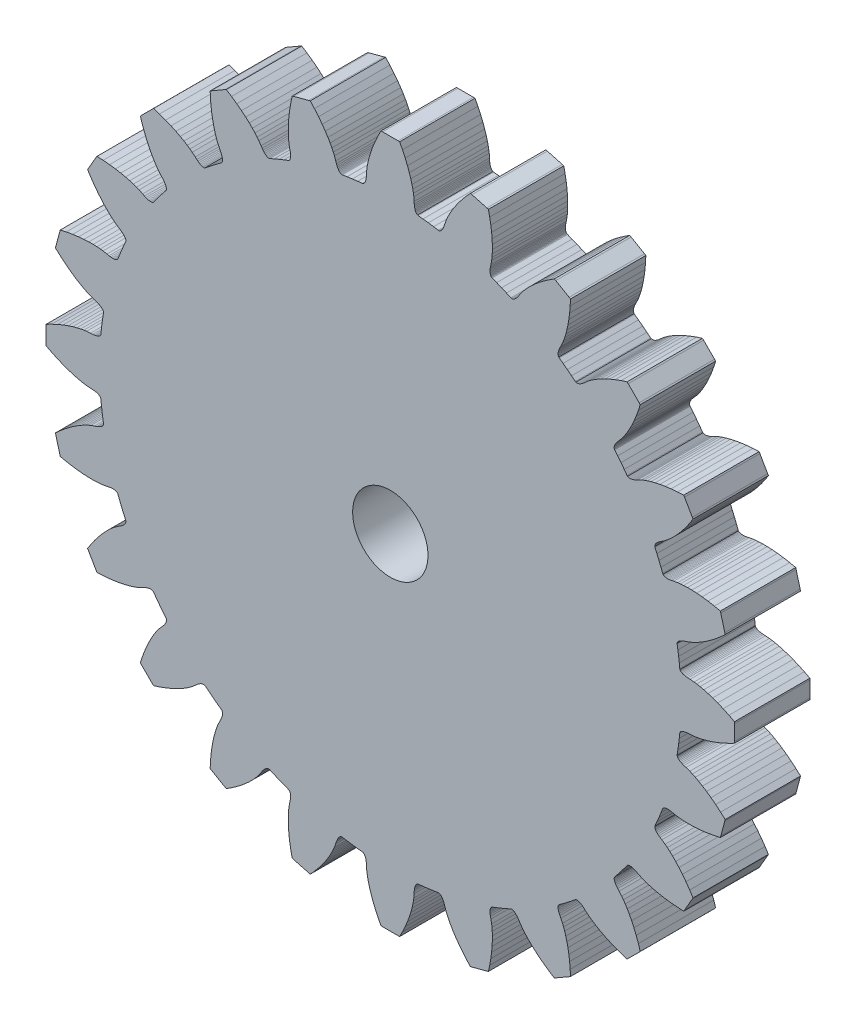
SolidWorks part; units mm, degrees
ref_plane "Front Plane" through (0, 0, 0) normal (0, 0, 1) x (1, 0, 0)
ref_plane "Top Plane" through (0, 0, 0) normal (0, 1, 0) x (1, 0, 0)
ref_plane "Right Plane" through (0, 0, 0) normal (1, 0, 0) x (0, 0, -1)
sketch "Sketch2" plane through (0, 0, 0) normal (0, 0, 1) x (1, 0, 0)
  line L1176 (3.2896, 23.0036) -> (3.0389, 22.7942)
  line L1177 (3.0389, 22.7942) -> (2.8021, 22.6117)
  line L1178 (2.8021, 22.6117) -> (2.5789, 22.4544)
  line L1179 (2.5789, 22.4544) -> (2.3725, 22.3218)
  line L1180 (2.3725, 22.3218) -> (2.182, 22.2103)
  line L1181 (2.182, 22.2103) -> (2.0109, 22.1191)
  line L1182 (2.0109, 22.1191) -> (1.8618, 22.048)
  line L1183 (1.8618, 22.048) -> (1.7314, 21.9922)
  line L1184 (1.7314, 21.9922) -> (1.5416, 21.9241)
  line L1185 (1.5416, 21.9241) -> (1.4393, 21.8922)
  line L1186 (1.4393, 21.8922) -> (1.3698, 21.8662)
  line L1187 (1.3698, 21.8662) -> (1.3083, 21.8387)
  line L1188 (1.3083, 21.8387) -> (1.2546, 21.8097)
  line L1189 (1.2546, 21.8097) -> (1.2083, 21.7799)
  line L1190 (1.2083, 21.7799) -> (1.1698, 21.7495)
  line L1191 (1.1698, 21.7495) -> (1.1387, 21.7184)
  line L1192 (1.1387, 21.7184) -> (1.1155, 21.6879)
  line L1193 (1.1155, 21.6879) -> (1.1004, 21.6575)
  line L1194 (1.1004, 21.6575) -> (1.0924, 21.627)
  line L1195 (1.0924, 21.627) -> (1.093, 21.5916)
  line L1196 (1.093, 21.5916) -> (1.1307, 21.3526)
  line L1197 (1.1307, 21.3526) -> (1.1683, 21.0852)
  line L1198 (1.1683, 21.0852) -> (1.2011, 20.818)
  line L1199 (1.2011, 20.818) -> (1.2264, 20.5774)
  line L1200 (1.2264, 20.5774) -> (1.2351, 20.542)
  line L1201 (1.2351, 20.542) -> (1.2503, 20.5151)
  line L1202 (1.2503, 20.5151) -> (1.2736, 20.4896)
  line L1203 (1.2736, 20.4896) -> (1.304, 20.4665)
  line L1204 (1.304, 20.4665) -> (1.3417, 20.4448)
  line L1205 (1.3417, 20.4448) -> (1.3865, 20.4253)
  line L1206 (1.3865, 20.4253) -> (1.4393, 20.4086)
  line L1207 (1.4393, 20.4086) -> (1.4988, 20.3942)
  line L1208 (1.4988, 20.3942) -> (1.5655, 20.384)
  line L1209 (1.5655, 20.384) -> (1.6388, 20.3767)
  line L1210 (1.6388, 20.3767) -> (1.7459, 20.3724)
  line L1211 (1.7459, 20.3724) -> (1.9474, 20.3558)
  line L1212 (1.9474, 20.3558) -> (2.0872, 20.3354)
  line L1213 (2.0872, 20.3354) -> (2.2499, 20.305)
  line L1214 (2.2499, 20.305) -> (2.4391, 20.2616)
  line L1215 (2.4391, 20.2616) -> (2.6514, 20.203)
  line L1216 (2.6514, 20.203) -> (2.8854, 20.1275)
  line L1217 (2.8854, 20.1275) -> (3.1418, 20.034)
  line L1218 (3.1418, 20.034) -> (3.4178, 19.9188)
  line L1219 (3.4178, 19.9188) -> (3.7134, 19.7813)
  line L1220 (3.7134, 19.7813) -> (3.9915, 19.6379)
  line L1221 (3.9915, 19.6379) -> (3.9938, 19.5596)
  line L1222 (3.9938, 19.5596) -> (3.9938, 18.7742)
  line L1223 (3.9938, 18.7742) -> (3.9915, 18.6954)
  line L1224 (3.9915, 18.6954) -> (3.7134, 18.5525)
  line L1225 (3.7134, 18.5525) -> (3.4178, 18.415)
  line L1226 (3.4178, 18.415) -> (3.1418, 18.2998)
  line L1227 (3.1418, 18.2998) -> (2.8854, 18.2056)
  line L1228 (2.8854, 18.2056) -> (2.6514, 18.131)
  line L1229 (2.6514, 18.131) -> (2.4391, 18.0722)
  line L1230 (2.4391, 18.0722) -> (2.2499, 18.0288)
  line L1231 (2.2499, 18.0288) -> (2.0872, 17.9984)
  line L1232 (2.0872, 17.9984) -> (1.9474, 17.9781)
  line L1233 (1.9474, 17.9781) -> (1.7459, 17.9616)
  line L1234 (1.7459, 17.9616) -> (1.6388, 17.9571)
  line L1235 (1.6388, 17.9571) -> (1.5655, 17.9498)
  line L1236 (1.5655, 17.9498) -> (1.4988, 17.9391)
  line L1237 (1.4988, 17.9391) -> (1.4393, 17.9252)
  line L1238 (1.4393, 17.9252) -> (1.3865, 17.9085)
  line L1239 (1.3865, 17.9085) -> (1.3417, 17.889)
  line L1240 (1.3417, 17.889) -> (1.304, 17.8673)
  line L1241 (1.304, 17.8673) -> (1.2736, 17.8434)
  line L1242 (1.2736, 17.8434) -> (1.2503, 17.818)
  line L1243 (1.2503, 17.818) -> (1.2351, 17.7913)
  line L1244 (1.2351, 17.7913) -> (1.2264, 17.7565)
  line L1245 (1.2264, 17.7565) -> (1.2011, 17.516)
  line L1246 (1.2011, 17.516) -> (1.1683, 17.2478)
  line L1247 (1.1683, 17.2478) -> (1.1307, 16.9813)
  line L1248 (1.1307, 16.9813) -> (1.093, 16.7423)
  line L1249 (1.093, 16.7423) -> (1.0924, 16.706)
  line L1250 (1.0924, 16.706) -> (1.1004, 16.6763)
  line L1251 (1.1004, 16.6763) -> (1.1155, 16.6459)
  line L1252 (1.1155, 16.6459) -> (1.1387, 16.6155)
  line L1253 (1.1387, 16.6155) -> (1.1698, 16.5843)
  line L1254 (1.1698, 16.5843) -> (1.2083, 16.5539)
  line L1255 (1.2083, 16.5539) -> (1.2546, 16.5243)
  line L1256 (1.2546, 16.5243) -> (1.3083, 16.4953)
  line L1257 (1.3083, 16.4953) -> (1.3698, 16.4676)
  line L2458 (1.3698, 16.4676) -> (1.4393, 16.4416)
  line L2459 (1.4393, 16.4416) -> (1.5416, 16.4097)
  line L2460 (1.5416, 16.4097) -> (1.7314, 16.3416)
  line L2461 (1.7314, 16.3416) -> (1.8618, 16.2859)
  line L2462 (1.8618, 16.2859) -> (2.0109, 16.2142)
  line L2463 (2.0109, 16.2142) -> (2.182, 16.1235)
  line L2464 (2.182, 16.1235) -> (2.3725, 16.012)
  line L2465 (2.3725, 16.012) -> (2.5789, 15.8788)
  line L2466 (2.5789, 15.8788) -> (2.8021, 15.7215)
  line L2467 (2.8021, 15.7215) -> (3.0389, 15.5396)
  line L2468 (3.0389, 15.5396) -> (3.2896, 15.3296)
  line L2469 (3.2896, 15.3296) -> (3.5207, 15.1195)
  line L2470 (3.5207, 15.1195) -> (3.5018, 15.0434)
  line L2471 (3.5018, 15.0434) -> (3.2991, 14.2842)
  line L2472 (3.2991, 14.2842) -> (3.2766, 14.2089)
  line L2473 (3.2766, 14.2089) -> (2.9715, 14.1429)
  line L2474 (2.9715, 14.1429) -> (2.65, 14.0864)
  line L2475 (2.65, 14.0864) -> (2.3537, 14.0466)
  line L2476 (2.3537, 14.0466) -> (2.0811, 14.0219)
  line L2477 (2.0811, 14.0219) -> (1.8364, 14.0105)
  line L2478 (1.8364, 14.0105) -> (1.6155, 14.009)
  line L2479 (1.6155, 14.009) -> (1.4221, 14.0155)
  line L2480 (1.4221, 14.0155) -> (1.2569, 14.0285)
  line L2481 (1.2569, 14.0285) -> (1.1163, 14.0452)
  line L2482 (1.1163, 14.0452) -> (0.9179, 14.0814)
  line L2483 (0.9179, 14.0814) -> (0.8126, 14.1046)
  line L2484 (0.8126, 14.1046) -> (0.7404, 14.1169)
  line L2485 (0.7404, 14.1169) -> (0.6731, 14.1234)
  line L2486 (0.6731, 14.1234) -> (0.6121, 14.1256)
  line L2487 (0.6121, 14.1256) -> (0.5572, 14.1226)
  line L2488 (0.5572, 14.1226) -> (0.5086, 14.1162)
  line L2489 (0.5086, 14.1162) -> (0.4664, 14.1046)
  line L2490 (0.4664, 14.1046) -> (0.431, 14.0894)
  line L2491 (0.431, 14.0894) -> (0.402, 14.0712)
  line L2492 (0.402, 14.0712) -> (0.3801, 14.0488)
  line L2493 (0.3801, 14.0488) -> (0.3629, 14.0177)
  line L2494 (0.3629, 14.0177) -> (0.276, 13.7916)
  line L2495 (0.276, 13.7916) -> (0.1753, 13.5416)
  line L2496 (0.1753, 13.5416) -> (0.0703, 13.2939)
  line L2497 (0.0703, 13.2939) -> (-0.0283, 13.0723)
  line L2498 (-0.0283, 13.0723) -> (-0.0383, 13.0382)
  line L2499 (-0.0383, 13.0382) -> (-0.0383, 13.007)
  line L2500 (-0.0383, 13.007) -> (-0.0311, 12.9737)
  line L2501 (-0.0311, 12.9737) -> (-0.0167, 12.9376)
  line L2502 (-0.0167, 12.9376) -> (0.0051, 12.8999)
  line L2503 (0.0051, 12.8999) -> (0.0339, 12.8608)
  line L2504 (0.0339, 12.8608) -> (0.0709, 12.8202)
  line L2505 (0.0709, 12.8202) -> (0.1159, 12.7781)
  line L2506 (0.1159, 12.7781) -> (0.1681, 12.7354)
  line L2507 (0.1681, 12.7354) -> (0.2282, 12.6927)
  line L2508 (0.2282, 12.6927) -> (0.3186, 12.6354)
  line L2509 (0.3186, 12.6354) -> (0.4846, 12.5202)
  line L2510 (0.4846, 12.5202) -> (0.5955, 12.4326)
  line L2511 (0.5955, 12.4326) -> (0.7214, 12.3254)
  line L2512 (0.7214, 12.3254) -> (0.8635, 12.1928)
  line L2513 (0.8635, 12.1928) -> (1.0185, 12.0356)
  line L2514 (1.0185, 12.0356) -> (1.1836, 11.8538)
  line L2515 (1.1836, 11.8538) -> (1.3582, 11.6444)
  line L2516 (1.3582, 11.6444) -> (1.5401, 11.4068)
  line L2517 (1.5401, 11.4068) -> (1.727, 11.1395)
  line L2518 (1.727, 11.1395) -> (1.8965, 10.8765)
  line L2519 (1.8965, 10.8765) -> (1.8588, 10.8077)
  line L2520 (1.8588, 10.8077) -> (1.4663, 10.1281)
  line L2521 (1.4663, 10.1281) -> (1.4257, 10.0608)
  line L2522 (1.4257, 10.0608) -> (1.1128, 10.0753)
  line L2523 (1.1128, 10.0753) -> (0.7882, 10.1042)
  line L2524 (0.7882, 10.1042) -> (0.4911, 10.1426)
  line L2525 (0.4911, 10.1426) -> (0.2224, 10.1897)
  line L2526 (0.2224, 10.1897) -> (-0.0174, 10.2412)
  line L2527 (-0.0174, 10.2412) -> (-0.231, 10.2969)
  line L2528 (-0.231, 10.2969) -> (-0.4165, 10.3542)
  line L2529 (-0.4165, 10.3542) -> (-0.573, 10.4092)
  line L2530 (-0.573, 10.4092) -> (-0.7041, 10.4614)
  line L2531 (-0.7041, 10.4614) -> (-0.8868, 10.5476)
  line L2532 (-0.8868, 10.5476) -> (-0.9816, 10.5976)
  line L2533 (-0.9816, 10.5976) -> (-1.0492, 10.628)
  line L2534 (-1.0492, 10.628) -> (-1.1119, 10.6519)
  line L2535 (-1.1119, 10.6519) -> (-1.1708, 10.6693)
  line L2536 (-1.1708, 10.6693) -> (-1.2243, 10.6809)
  line L2537 (-1.2243, 10.6809) -> (-1.2729, 10.6867)
  line L2538 (-1.2729, 10.6867) -> (-1.3163, 10.6867)
  line L2539 (-1.3163, 10.6867) -> (-1.3548, 10.6816)
  line L2540 (-1.3548, 10.6816) -> (-1.3874, 10.6715)
  line L2541 (-1.3874, 10.6715) -> (-1.4141, 10.6555)
  line L2542 (-1.4141, 10.6555) -> (-1.4388, 10.6295)
  line L2543 (-1.4388, 10.6295) -> (-1.5809, 10.4339)
  line L2544 (-1.5809, 10.4339) -> (-1.7431, 10.2187)
  line L2545 (-1.7431, 10.2187) -> (-1.9089, 10.0064)
  line L2546 (-1.9089, 10.0064) -> (-2.0618, 9.8181)
  line L2547 (-2.0618, 9.8181) -> (-2.0799, 9.7877)
  line L2548 (-2.0799, 9.7877) -> (-2.0885, 9.7572)
  line L2549 (-2.0885, 9.7572) -> (-2.09, 9.7232)
  line L2550 (-2.09, 9.7232) -> (-2.0856, 9.6848)
  line L2551 (-2.0856, 9.6848) -> (-2.0741, 9.6428)
  line L2552 (-2.0741, 9.6428) -> (-2.056, 9.5971)
  line L2553 (-2.056, 9.5971) -> (-2.0307, 9.5486)
  line L2554 (-2.0307, 9.5486) -> (-1.9988, 9.4964)
  line L2555 (-1.9988, 9.4964) -> (-1.959, 9.4421)
  line L2556 (-1.959, 9.4421) -> (-1.9119, 9.3849)
  line L2557 (-1.9119, 9.3849) -> (-1.8394, 9.3059)
  line L2558 (-1.8394, 9.3059) -> (-1.7089, 9.1516)
  line L2559 (-1.7089, 9.1516) -> (-1.6243, 9.0386)
  line L2560 (-1.6243, 9.0386) -> (-1.5308, 8.9017)
  line L2561 (-1.5308, 8.9017) -> (-1.428, 8.7372)
  line L2562 (-1.428, 8.7372) -> (-1.3186, 8.546)
  line L2563 (-1.3186, 8.546) -> (-1.2062, 8.3272)
  line L2564 (-1.2062, 8.3272) -> (-1.0917, 8.0794)
  line L2565 (-1.0917, 8.0794) -> (-0.9773, 7.8034)
  line L2566 (-0.9773, 7.8034) -> (-0.8657, 7.497)
  line L2567 (-0.8657, 7.497) -> (-0.7709, 7.1985)
  line L2568 (-0.7709, 7.1985) -> (-0.8252, 7.142)
  line L2569 (-0.8252, 7.142) -> (-1.3802, 6.5871)
  line L2570 (-1.3802, 6.5871) -> (-1.4365, 6.5328)
  line L2571 (-1.4365, 6.5328) -> (-1.7351, 6.6277)
  line L2572 (-1.7351, 6.6277) -> (-2.0415, 6.7392)
  line L2573 (-2.0415, 6.7392) -> (-2.3174, 6.8537)
  line L2574 (-2.3174, 6.8537) -> (-2.5652, 6.9682)
  line L2575 (-2.5652, 6.9682) -> (-2.7841, 7.0805)
  line L2576 (-2.7841, 7.0805) -> (-2.9753, 7.1898)
  line L2577 (-2.9753, 7.1898) -> (-3.1398, 7.2927)
  line L2578 (-3.1398, 7.2927) -> (-3.2767, 7.3862)
  line L2579 (-3.2767, 7.3862) -> (-3.3898, 7.4709)
  line L2580 (-3.3898, 7.4709) -> (-3.544, 7.6013)
  line L2581 (-3.544, 7.6013) -> (-3.623, 7.6738)
  line L2582 (-3.623, 7.6738) -> (-3.6802, 7.7209)
  line L2583 (-3.6802, 7.7209) -> (-3.7345, 7.7607)
  line L2584 (-3.7345, 7.7607) -> (-3.7866, 7.7926)
  line L2585 (-3.7866, 7.7926) -> (-3.8352, 7.8179)
  line L2586 (-3.8352, 7.8179) -> (-3.8809, 7.836)
  line L2587 (-3.8809, 7.836) -> (-3.9229, 7.8476)
  line L2588 (-3.9229, 7.8476) -> (-3.9613, 7.852)
  line L2589 (-3.9613, 7.852) -> (-3.9953, 7.8505)
  line L2590 (-3.9953, 7.8505) -> (-4.0256, 7.8418)
  line L2591 (-4.0256, 7.8418) -> (-4.0561, 7.8237)
  line L2592 (-4.0561, 7.8237) -> (-4.2445, 7.6709)
  line L2593 (-4.2445, 7.6709) -> (-4.4569, 7.505)
  line L2594 (-4.4569, 7.505) -> (-4.672, 7.3427)
  line L2595 (-4.672, 7.3427) -> (-4.8674, 7.2007)
  line L2596 (-4.8674, 7.2007) -> (-4.8936, 7.1761)
  line L2597 (-4.8936, 7.1761) -> (-4.9096, 7.1493)
  line L2598 (-4.9096, 7.1493) -> (-4.9197, 7.1167)
  line L2599 (-4.9197, 7.1167) -> (-4.9248, 7.0783)
  line L2600 (-4.9248, 7.0783) -> (-4.9248, 7.0348)
  line L2601 (-4.9248, 7.0348) -> (-4.9191, 6.9863)
  line L2602 (-4.9191, 6.9863) -> (-4.9073, 6.9327)
  line L2603 (-4.9073, 6.9327) -> (-4.8901, 6.874)
  line L2604 (-4.8901, 6.874) -> (-4.8662, 6.8109)
  line L2605 (-4.8662, 6.8109) -> (-4.8357, 6.7436)
  line L2606 (-4.8357, 6.7436) -> (-4.7857, 6.6487)
  line L2607 (-4.7857, 6.6487) -> (-4.6994, 6.4661)
  line L2608 (-4.6994, 6.4661) -> (-4.6473, 6.335)
  line L2609 (-4.6473, 6.335) -> (-4.5922, 6.1785)
  line L2610 (-4.5922, 6.1785) -> (-4.5349, 5.9931)
  line L2611 (-4.5349, 5.9931) -> (-4.4794, 5.7793)
  line L2612 (-4.4794, 5.7793) -> (-4.4277, 5.5396)
  line L2613 (-4.4277, 5.5396) -> (-4.3807, 5.2708)
  line L2614 (-4.3807, 5.2708) -> (-4.3422, 4.9738)
  line L2615 (-4.3422, 4.9738) -> (-4.3134, 4.6492)
  line L2616 (-4.3134, 4.6492) -> (-4.2988, 4.3363)
  line L2617 (-4.2988, 4.3363) -> (-4.3661, 4.2957)
  line L2618 (-4.3661, 4.2957) -> (-5.0456, 3.9031)
  line L2619 (-5.0456, 3.9031) -> (-5.1144, 3.8654)
  line L2620 (-5.1144, 3.8654) -> (-5.3775, 4.0349)
  line L2621 (-5.3775, 4.0349) -> (-5.6449, 4.2218)
  line L2622 (-5.6449, 4.2218) -> (-5.8825, 4.4037)
  line L2623 (-5.8825, 4.4037) -> (-6.0918, 4.5782)
  line L2624 (-6.0918, 4.5782) -> (-6.2736, 4.7434)
  line L2625 (-6.2736, 4.7434) -> (-6.4309, 4.8984)
  line L2626 (-6.4309, 4.8984) -> (-6.5635, 5.0404)
  line L2627 (-6.5635, 5.0404) -> (-6.6707, 5.1665)
  line L2628 (-6.6707, 5.1665) -> (-6.7584, 5.2773)
  line L2629 (-6.7584, 5.2773) -> (-6.8735, 5.4432)
  line L2630 (-6.8735, 5.4432) -> (-6.9307, 5.5338)
  line L2631 (-6.9307, 5.5338) -> (-6.9735, 5.5939)
  line L2632 (-6.9735, 5.5939) -> (-7.0161, 5.6461)
  line L2633 (-7.0161, 5.6461) -> (-7.0582, 5.691)
  line L2634 (-7.0582, 5.691) -> (-7.0989, 5.7279)
  line L2635 (-7.0989, 5.7279) -> (-7.138, 5.7569)
  line L2636 (-7.138, 5.7569) -> (-7.1757, 5.7786)
  line L2637 (-7.1757, 5.7786) -> (-7.2117, 5.7931)
  line L2638 (-7.2117, 5.7931) -> (-7.2451, 5.8004)
  line L2639 (-7.2451, 5.8004) -> (-7.2764, 5.8004)
  line L2640 (-7.2764, 5.8004) -> (-7.3103, 5.7902)
  line L2641 (-7.3103, 5.7902) -> (-7.5321, 5.6917)
  line L2642 (-7.5321, 5.6917) -> (-7.7799, 5.5867)
  line L2643 (-7.7799, 5.5867) -> (-8.0296, 5.486)
  line L2644 (-8.0296, 5.486) -> (-8.2557, 5.399)
  line L2645 (-8.2557, 5.399) -> (-8.2869, 5.3816)
  line L2646 (-8.2869, 5.3816) -> (-8.3093, 5.3599)
  line L2647 (-8.3093, 5.3599) -> (-8.3275, 5.3309)
  line L2648 (-8.3275, 5.3309) -> (-8.3427, 5.2954)
  line L2649 (-8.3427, 5.2954) -> (-8.3542, 5.2534)
  line L2650 (-8.3542, 5.2534) -> (-8.3607, 5.2049)
  line L2651 (-8.3607, 5.2049) -> (-8.3637, 5.1498)
  line L2652 (-8.3637, 5.1498) -> (-8.3614, 5.089)
  line L2653 (-8.3614, 5.089) -> (-8.355, 5.0216)
  line L2654 (-8.355, 5.0216) -> (-8.3427, 4.9492)
  line L2655 (-8.3427, 4.9492) -> (-8.3195, 4.8441)
  line L2656 (-8.3195, 4.8441) -> (-8.2832, 4.6456)
  line L2657 (-8.2832, 4.6456) -> (-8.2666, 4.5051)
  line L2658 (-8.2666, 4.5051) -> (-8.2535, 4.3399)
  line L2659 (-8.2535, 4.3399) -> (-8.247, 4.1465)
  line L2660 (-8.247, 4.1465) -> (-8.2485, 3.9255)
  line L2661 (-8.2485, 3.9255) -> (-8.2599, 3.6807)
  line L2662 (-8.2599, 3.6807) -> (-8.2846, 3.4083)
  line L2663 (-8.2846, 3.4083) -> (-8.3246, 3.112)
  line L2664 (-8.3246, 3.112) -> (-8.381, 2.7903)
  line L2665 (-8.381, 2.7903) -> (-8.4469, 2.4853)
  line L2666 (-8.4469, 2.4853) -> (-8.5222, 2.4629)
  line L2667 (-8.5222, 2.4629) -> (-9.2814, 2.2601)
  line L2668 (-9.2814, 2.2601) -> (-9.3575, 2.2412)
  line L2669 (-9.3575, 2.2412) -> (-9.5676, 2.4723)
  line L2670 (-9.5676, 2.4723) -> (-9.7777, 2.723)
  line L2671 (-9.7777, 2.723) -> (-9.9595, 2.9598)
  line L2672 (-9.9595, 2.9598) -> (-10.1168, 3.183)
  line L2673 (-10.1168, 3.183) -> (-10.2502, 3.3894)
  line L2674 (-10.2502, 3.3894) -> (-10.3615, 3.58)
  line L2675 (-10.3615, 3.58) -> (-10.4523, 3.7509)
  line L2676 (-10.4523, 3.7509) -> (-10.5239, 3.9002)
  line L2677 (-10.5239, 3.9002) -> (-10.5797, 4.0306)
  line L2678 (-10.5797, 4.0306) -> (-10.6477, 4.2204)
  line L2679 (-10.6477, 4.2204) -> (-10.6796, 4.3225)
  line L2680 (-10.6796, 4.3225) -> (-10.7058, 4.3921)
  line L2681 (-10.7058, 4.3921) -> (-10.7333, 4.4536)
  line L2682 (-10.7333, 4.4536) -> (-10.7624, 4.5072)
  line L2683 (-10.7624, 4.5072) -> (-10.792, 4.5536)
  line L2684 (-10.792, 4.5536) -> (-10.8225, 4.592)
  line L2685 (-10.8225, 4.592) -> (-10.8536, 4.6232)
  line L2686 (-10.8536, 4.6232) -> (-10.884, 4.6463)
  line L2687 (-10.884, 4.6463) -> (-10.9145, 4.6616)
  line L2688 (-10.9145, 4.6616) -> (-10.9441, 4.6695)
  line L2689 (-10.9441, 4.6695) -> (-10.9803, 4.6688)
  line L2690 (-10.9803, 4.6688) -> (-11.2193, 4.6311)
  line L2691 (-11.2193, 4.6311) -> (-11.486, 4.5935)
  line L2692 (-11.486, 4.5935) -> (-11.754, 4.5608)
  line L2693 (-11.754, 4.5608) -> (-11.9946, 4.5355)
  line L2694 (-11.9946, 4.5355) -> (-12.0294, 4.5268)
  line L2695 (-12.0294, 4.5268) -> (-12.0561, 4.5116)
  line L2696 (-12.0561, 4.5116) -> (-12.0815, 4.4884)
  line L2697 (-12.0815, 4.4884) -> (-12.1054, 4.458)
  line L2698 (-12.1054, 4.458) -> (-12.1272, 4.4203)
  line L2699 (-12.1272, 4.4203) -> (-12.1465, 4.3754)
  line L2700 (-12.1465, 4.3754) -> (-12.1632, 4.3225)
  line L2701 (-12.1632, 4.3225) -> (-12.1772, 4.2631)
  line L2702 (-12.1772, 4.2631) -> (-12.1879, 4.1965)
  line L2703 (-12.1879, 4.1965) -> (-12.1951, 4.1233)
  line L2704 (-12.1951, 4.1233) -> (-12.1997, 4.0161)
  line L2705 (-12.1997, 4.0161) -> (-12.2161, 3.8147)
  line L2706 (-12.2161, 3.8147) -> (-12.2365, 3.6749)
  line L2707 (-12.2365, 3.6749) -> (-12.267, 3.5119)
  line L2708 (-12.267, 3.5119) -> (-12.3104, 3.3228)
  line L2709 (-12.3104, 3.3228) -> (-12.3691, 3.1105)
  line L2710 (-12.3691, 3.1105) -> (-12.4436, 2.8765)
  line L2711 (-12.4436, 2.8765) -> (-12.5379, 2.6201)
  line L2712 (-12.5379, 2.6201) -> (-12.653, 2.3441)
  line L2713 (-12.653, 2.3441) -> (-12.7907, 2.0485)
  line L2714 (-12.7907, 2.0485) -> (-12.9334, 1.7703)
  line L2715 (-12.9334, 1.7703) -> (-13.0123, 1.7681)
  line L2716 (-13.0123, 1.7681) -> (-13.7977, 1.7681)
  line L2717 (-13.7977, 1.7681) -> (-13.876, 1.7703)
  line L2718 (-13.876, 1.7703) -> (-14.0193, 2.0485)
  line L2719 (-14.0193, 2.0485) -> (-14.1569, 2.3441)
  line L2720 (-14.1569, 2.3441) -> (-14.272, 2.6201)
  line L2721 (-14.272, 2.6201) -> (-14.3655, 2.8765)
  line L2722 (-14.3655, 2.8765) -> (-14.4411, 3.1105)
  line L2723 (-14.4411, 3.1105) -> (-14.4997, 3.3228)
  line L2724 (-14.4997, 3.3228) -> (-14.5431, 3.5119)
  line L2725 (-14.5431, 3.5119) -> (-14.5735, 3.6749)
  line L2726 (-14.5735, 3.6749) -> (-14.5938, 3.8147)
  line L2727 (-14.5938, 3.8147) -> (-14.6105, 4.0161)
  line L2728 (-14.6105, 4.0161) -> (-14.6148, 4.1233)
  line L2729 (-14.6148, 4.1233) -> (-14.622, 4.1965)
  line L2730 (-14.622, 4.1965) -> (-14.6322, 4.2631)
  line L2731 (-14.6322, 4.2631) -> (-14.6467, 4.3225)
  line L2732 (-14.6467, 4.3225) -> (-14.6634, 4.3754)
  line L2733 (-14.6634, 4.3754) -> (-14.6829, 4.4203)
  line L2734 (-14.6829, 4.4203) -> (-14.7047, 4.458)
  line L2735 (-14.7047, 4.458) -> (-14.7278, 4.4884)
  line L2736 (-14.7278, 4.4884) -> (-14.7533, 4.5116)
  line L2737 (-14.7533, 4.5116) -> (-14.78, 4.5268)
  line L2738 (-14.78, 4.5268) -> (-14.8155, 4.5355)
  line L2739 (-14.8155, 4.5355) -> (-15.056, 4.5608)
  line L2740 (-15.056, 4.5608) -> (-15.3233, 4.5935)
  line L2741 (-15.3233, 4.5935) -> (-15.5906, 4.6311)
  line L2742 (-15.5906, 4.6311) -> (-15.8296, 4.6688)
  line L2743 (-15.8296, 4.6688) -> (-15.8652, 4.6695)
  line L2744 (-15.8652, 4.6695) -> (-15.8956, 4.6616)
  line L2745 (-15.8956, 4.6616) -> (-15.926, 4.6463)
  line L2746 (-15.926, 4.6463) -> (-15.9565, 4.6232)
  line L2747 (-15.9565, 4.6232) -> (-15.9876, 4.592)
  line L2748 (-15.9876, 4.592) -> (-16.018, 4.5536)
  line L2749 (-16.018, 4.5536) -> (-16.0478, 4.5072)
  line L2750 (-16.0478, 4.5072) -> (-16.0768, 4.4536)
  line L2751 (-16.0768, 4.4536) -> (-16.1043, 4.3921)
  line L2752 (-16.1043, 4.3921) -> (-16.1303, 4.3225)
  line L2753 (-16.1303, 4.3225) -> (-16.1623, 4.2204)
  line L2754 (-16.1623, 4.2204) -> (-16.2304, 4.0306)
  line L2755 (-16.2304, 4.0306) -> (-16.286, 3.9002)
  line L2756 (-16.286, 3.9002) -> (-16.3571, 3.7509)
  line L2757 (-16.3571, 3.7509) -> (-16.4484, 3.58)
  line L2758 (-16.4484, 3.58) -> (-16.5599, 3.3894)
  line L2759 (-16.5599, 3.3894) -> (-16.6925, 3.183)
  line L2760 (-16.6925, 3.183) -> (-16.8497, 2.9598)
  line L2761 (-16.8497, 2.9598) -> (-17.0323, 2.723)
  line L2762 (-17.0323, 2.723) -> (-17.2416, 2.4723)
  line L2763 (-17.2416, 2.4723) -> (-17.4524, 2.2412)
  line L2764 (-17.4524, 2.2412) -> (-17.5292, 2.2601)
  line L2765 (-17.5292, 2.2601) -> (-18.2878, 2.4629)
  line L2766 (-18.2878, 2.4629) -> (-18.3624, 2.4853)
  line L2767 (-18.3624, 2.4853) -> (-18.429, 2.7903)
  line L2768 (-18.429, 2.7903) -> (-18.4855, 3.112)
  line L2769 (-18.4855, 3.112) -> (-18.5246, 3.4083)
  line L2770 (-18.5246, 3.4083) -> (-18.5492, 3.6807)
  line L2771 (-18.5492, 3.6807) -> (-18.5615, 3.9255)
  line L2772 (-18.5615, 3.9255) -> (-18.563, 4.1465)
  line L2773 (-18.563, 4.1465) -> (-18.5557, 4.3399)
  line L2774 (-18.5557, 4.3399) -> (-18.5435, 4.5051)
  line L2775 (-18.5435, 4.5051) -> (-18.5261, 4.6456)
  line L2776 (-18.5261, 4.6456) -> (-18.4906, 4.8441)
  line L2777 (-18.4906, 4.8441) -> (-18.4667, 4.9492)
  line L2778 (-18.4667, 4.9492) -> (-18.4551, 5.0216)
  line L2779 (-18.4551, 5.0216) -> (-18.4479, 5.089)
  line L2780 (-18.4479, 5.089) -> (-18.4464, 5.1498)
  line L2781 (-18.4464, 5.1498) -> (-18.4485, 5.2049)
  line L2782 (-18.4485, 5.2049) -> (-18.4557, 5.2534)
  line L2783 (-18.4557, 5.2534) -> (-18.4674, 5.2954)
  line L2784 (-18.4674, 5.2954) -> (-18.4819, 5.3309)
  line L2785 (-18.4819, 5.3309) -> (-18.5007, 5.3599)
  line L2786 (-18.5007, 5.3599) -> (-18.5225, 5.3816)
  line L2787 (-18.5225, 5.3816) -> (-18.5543, 5.399)
  line L2788 (-18.5543, 5.399) -> (-18.7803, 5.486)
  line L2789 (-18.7803, 5.486) -> (-19.0303, 5.5867)
  line L2790 (-19.0303, 5.5867) -> (-19.278, 5.6917)
  line L2791 (-19.278, 5.6917) -> (-19.499, 5.7902)
  line L2792 (-19.499, 5.7902) -> (-19.5337, 5.8004)
  line L2793 (-19.5337, 5.8004) -> (-19.565, 5.8004)
  line L2794 (-19.565, 5.8004) -> (-19.5982, 5.7931)
  line L2795 (-19.5982, 5.7931) -> (-19.6337, 5.7786)
  line L2796 (-19.6337, 5.7786) -> (-19.6714, 5.7569)
  line L2797 (-19.6714, 5.7569) -> (-19.7112, 5.7279)
  line L2798 (-19.7112, 5.7279) -> (-19.7518, 5.691)
  line L2799 (-19.7518, 5.691) -> (-19.7938, 5.6461)
  line L2800 (-19.7938, 5.6461) -> (-19.8358, 5.5939)
  line L2801 (-19.8358, 5.5939) -> (-19.8793, 5.5338)
  line L2802 (-19.8793, 5.5338) -> (-19.9365, 5.4432)
  line L2803 (-19.9365, 5.4432) -> (-20.0517, 5.2773)
  line L2804 (-20.0517, 5.2773) -> (-20.1386, 5.1665)
  line L2805 (-20.1386, 5.1665) -> (-20.2466, 5.0404)
  line L2806 (-20.2466, 5.0404) -> (-20.3792, 4.8984)
  line L2807 (-20.3792, 4.8984) -> (-20.5356, 4.7434)
  line L2808 (-20.5356, 4.7434) -> (-20.7175, 4.5782)
  line L2809 (-20.7175, 4.5782) -> (-20.9276, 4.4037)
  line L2810 (-20.9276, 4.4037) -> (-21.1645, 4.2218)
  line L2811 (-21.1645, 4.2218) -> (-21.4318, 4.0349)
  line L2812 (-21.4318, 4.0349) -> (-21.6955, 3.8654)
  line L2813 (-21.6955, 3.8654) -> (-21.765, 3.9031)
  line L2814 (-21.765, 3.9031) -> (-22.4445, 4.2957)
  line L2815 (-22.4445, 4.2957) -> (-22.5112, 4.3363)
  line L2816 (-22.5112, 4.3363) -> (-22.496, 4.6492)
  line L2817 (-22.496, 4.6492) -> (-22.4677, 4.9738)
  line L2818 (-22.4677, 4.9738) -> (-22.4286, 5.2708)
  line L2819 (-22.4286, 5.2708) -> (-22.3822, 5.5396)
  line L2820 (-22.3822, 5.5396) -> (-22.3301, 5.7793)
  line L2821 (-22.3301, 5.7793) -> (-22.2743, 5.9931)
  line L2822 (-22.2743, 5.9931) -> (-22.2178, 6.1785)
  line L2823 (-22.2178, 6.1785) -> (-22.1627, 6.335)
  line L2824 (-22.1627, 6.335) -> (-22.1106, 6.4661)
  line L2825 (-22.1106, 6.4661) -> (-22.0244, 6.6487)
  line L2826 (-22.0244, 6.6487) -> (-21.9744, 6.7436)
  line L2827 (-21.9744, 6.7436) -> (-21.9439, 6.8109)
  line L2828 (-21.9439, 6.8109) -> (-21.92, 6.874)
  line L2829 (-21.92, 6.874) -> (-21.9019, 6.9327)
  line L2830 (-21.9019, 6.9327) -> (-21.8903, 6.9863)
  line L2831 (-21.8903, 6.9863) -> (-21.8846, 7.0348)
  line L2832 (-21.8846, 7.0348) -> (-21.8846, 7.0783)
  line L2833 (-21.8846, 7.0783) -> (-21.8903, 7.1167)
  line L2834 (-21.8903, 7.1167) -> (-21.9005, 7.1493)
  line L2835 (-21.9005, 7.1493) -> (-21.9164, 7.1761)
  line L2836 (-21.9164, 7.1761) -> (-21.9418, 7.2007)
  line L2837 (-21.9418, 7.2007) -> (-22.1381, 7.3427)
  line L2838 (-22.1381, 7.3427) -> (-22.3532, 7.505)
  line L2839 (-22.3532, 7.505) -> (-22.5655, 7.6709)
  line L2840 (-22.5655, 7.6709) -> (-22.7539, 7.8237)
  line L2841 (-22.7539, 7.8237) -> (-22.7843, 7.8418)
  line L2842 (-22.7843, 7.8418) -> (-22.814, 7.8505)
  line L2843 (-22.814, 7.8505) -> (-22.8488, 7.852)
  line L2844 (-22.8488, 7.852) -> (-22.8864, 7.8476)
  line L2845 (-22.8864, 7.8476) -> (-22.9285, 7.836)
  line L2846 (-22.9285, 7.836) -> (-22.9741, 7.8179)
  line L2847 (-22.9741, 7.8179) -> (-23.0234, 7.7926)
  line L2848 (-23.0234, 7.7926) -> (-23.0755, 7.7607)
  line L2849 (-23.0755, 7.7607) -> (-23.1298, 7.7209)
  line L2850 (-23.1298, 7.7209) -> (-23.1871, 7.6738)
  line L2851 (-23.1871, 7.6738) -> (-23.266, 7.6013)
  line L2852 (-23.266, 7.6013) -> (-23.4196, 7.4709)
  line L2853 (-23.4196, 7.4709) -> (-23.5334, 7.3862)
  line L2854 (-23.5334, 7.3862) -> (-23.6696, 7.2927)
  line L2855 (-23.6696, 7.2927) -> (-23.834, 7.1898)
  line L2856 (-23.834, 7.1898) -> (-24.026, 7.0805)
  line L2857 (-24.026, 7.0805) -> (-24.244, 6.9682)
  line L2858 (-24.244, 6.9682) -> (-24.4918, 6.8537)
  line L2859 (-24.4918, 6.8537) -> (-24.7685, 6.7392)
  line L2860 (-24.7685, 6.7392) -> (-25.075, 6.6277)
  line L2861 (-25.075, 6.6277) -> (-25.3727, 6.5328)
  line L2862 (-25.3727, 6.5328) -> (-25.4299, 6.5871)
  line L2863 (-25.4299, 6.5871) -> (-25.9856, 7.142)
  line L2864 (-25.9856, 7.142) -> (-26.0392, 7.1985)
  line L2865 (-26.0392, 7.1985) -> (-25.9443, 7.497)
  line L2866 (-25.9443, 7.497) -> (-25.832, 7.8034)
  line L2867 (-25.832, 7.8034) -> (-25.7183, 8.0794)
  line L2868 (-25.7183, 8.0794) -> (-25.6031, 8.3272)
  line L2869 (-25.6031, 8.3272) -> (-25.4908, 8.546)
  line L2870 (-25.4908, 8.546) -> (-25.3821, 8.7372)
  line L2871 (-25.3821, 8.7372) -> (-25.2793, 8.9017)
  line L2872 (-25.2793, 8.9017) -> (-25.1858, 9.0386)
  line L2873 (-25.1858, 9.0386) -> (-25.101, 9.1516)
  line L2874 (-25.101, 9.1516) -> (-24.9706, 9.3059)
  line L2875 (-24.9706, 9.3059) -> (-24.8975, 9.3849)
  line L2876 (-24.8975, 9.3849) -> (-24.8511, 9.4421)
  line L2877 (-24.8511, 9.4421) -> (-24.8113, 9.4964)
  line L2878 (-24.8113, 9.4964) -> (-24.7794, 9.5486)
  line L2879 (-24.7794, 9.5486) -> (-24.754, 9.5971)
  line L2880 (-24.754, 9.5971) -> (-24.7359, 9.6428)
  line L2881 (-24.7359, 9.6428) -> (-24.7243, 9.6848)
  line L2882 (-24.7243, 9.6848) -> (-24.72, 9.7232)
  line L2883 (-24.72, 9.7232) -> (-24.7214, 9.7572)
  line L2884 (-24.7214, 9.7572) -> (-24.7294, 9.7877)
  line L2885 (-24.7294, 9.7877) -> (-24.7482, 9.8181)
  line L2886 (-24.7482, 9.8181) -> (-24.9004, 10.0064)
  line L2887 (-24.9004, 10.0064) -> (-25.0663, 10.2187)
  line L2888 (-25.0663, 10.2187) -> (-25.2285, 10.4339)
  line L2889 (-25.2285, 10.4339) -> (-25.3713, 10.6295)
  line L2890 (-25.3713, 10.6295) -> (-25.3959, 10.6555)
  line L2891 (-25.3959, 10.6555) -> (-25.4227, 10.6715)
  line L2892 (-25.4227, 10.6715) -> (-25.4553, 10.6816)
  line L2893 (-25.4553, 10.6816) -> (-25.493, 10.6867)
  line L2894 (-25.493, 10.6867) -> (-25.5372, 10.6867)
  line L2895 (-25.5372, 10.6867) -> (-25.5857, 10.6809)
  line L2896 (-25.5857, 10.6809) -> (-25.6393, 10.6693)
  line L2897 (-25.6393, 10.6693) -> (-25.698, 10.6519)
  line L2898 (-25.698, 10.6519) -> (-25.761, 10.628)
  line L2899 (-25.761, 10.628) -> (-25.8284, 10.5976)
  line L2900 (-25.8284, 10.5976) -> (-25.9233, 10.5476)
  line L2901 (-25.9233, 10.5476) -> (-26.1058, 10.4614)
  line L2902 (-26.1058, 10.4614) -> (-26.237, 10.4092)
  line L2903 (-26.237, 10.4092) -> (-26.3934, 10.3542)
  line L2904 (-26.3934, 10.3542) -> (-26.5789, 10.2969)
  line L2905 (-26.5789, 10.2969) -> (-26.7919, 10.2412)
  line L2906 (-26.7919, 10.2412) -> (-27.0324, 10.1897)
  line L2907 (-27.0324, 10.1897) -> (-27.3012, 10.1426)
  line L2908 (-27.3012, 10.1426) -> (-27.5975, 10.1042)
  line L2909 (-27.5975, 10.1042) -> (-27.9227, 10.0753)
  line L2910 (-27.9227, 10.0753) -> (-28.235, 10.0608)
  line L2911 (-28.235, 10.0608) -> (-28.2762, 10.1281)
  line L2912 (-28.2762, 10.1281) -> (-28.6696, 10.8077)
  line L2913 (-28.6696, 10.8077) -> (-28.7066, 10.8765)
  line L2914 (-28.7066, 10.8765) -> (-28.5371, 11.1395)
  line L2915 (-28.5371, 11.1395) -> (-28.3501, 11.4068)
  line L2916 (-28.3501, 11.4068) -> (-28.1683, 11.6444)
  line L2917 (-28.1683, 11.6444) -> (-27.993, 11.8538)
  line L2918 (-27.993, 11.8538) -> (-27.8278, 12.0356)
  line L2919 (-27.8278, 12.0356) -> (-27.6735, 12.1928)
  line L2920 (-27.6735, 12.1928) -> (-27.5315, 12.3254)
  line L2921 (-27.5315, 12.3254) -> (-27.4055, 12.4326)
  line L2922 (-27.4055, 12.4326) -> (-27.2946, 12.5202)
  line L2923 (-27.2946, 12.5202) -> (-27.1287, 12.6354)
  line L2924 (-27.1287, 12.6354) -> (-27.0382, 12.6927)
  line L2925 (-27.0382, 12.6927) -> (-26.978, 12.7354)
  line L2926 (-26.978, 12.7354) -> (-26.9259, 12.7781)
  line L2927 (-26.9259, 12.7781) -> (-26.881, 12.8202)
  line L2928 (-26.881, 12.8202) -> (-26.844, 12.8608)
  line L2929 (-26.844, 12.8608) -> (-26.8143, 12.8999)
  line L2930 (-26.8143, 12.8999) -> (-26.7926, 12.9376)
  line L2931 (-26.7926, 12.9376) -> (-26.7781, 12.9737)
  line L2932 (-26.7781, 12.9737) -> (-26.7709, 13.007)
  line L2933 (-26.7709, 13.007) -> (-26.7716, 13.0382)
  line L2934 (-26.7716, 13.0382) -> (-26.781, 13.0723)
  line L2935 (-26.781, 13.0723) -> (-26.8803, 13.2939)
  line L2936 (-26.8803, 13.2939) -> (-26.9853, 13.5416)
  line L2937 (-26.9853, 13.5416) -> (-27.086, 13.7916)
  line L2938 (-27.086, 13.7916) -> (-27.1729, 14.0177)
  line L2939 (-27.1729, 14.0177) -> (-27.1903, 14.0488)
  line L2940 (-27.1903, 14.0488) -> (-27.212, 14.0712)
  line L2941 (-27.212, 14.0712) -> (-27.2403, 14.0894)
  line L2942 (-27.2403, 14.0894) -> (-27.2758, 14.1046)
  line L2943 (-27.2758, 14.1046) -> (-27.3185, 14.1162)
  line L2944 (-27.3185, 14.1162) -> (-27.3671, 14.1226)
  line L2945 (-27.3671, 14.1226) -> (-27.4221, 14.1256)
  line L2946 (-27.4221, 14.1256) -> (-27.483, 14.1234)
  line L2947 (-27.483, 14.1234) -> (-27.5496, 14.1169)
  line L2948 (-27.5496, 14.1169) -> (-27.6228, 14.1046)
  line L2949 (-27.6228, 14.1046) -> (-27.7271, 14.0814)
  line L2950 (-27.7271, 14.0814) -> (-27.9263, 14.0452)
  line L2951 (-27.9263, 14.0452) -> (-28.0662, 14.0285)
  line L2952 (-28.0662, 14.0285) -> (-28.232, 14.0155)
  line L2953 (-28.232, 14.0155) -> (-28.4255, 14.009)
  line L2954 (-28.4255, 14.009) -> (-28.6457, 14.0105)
  line L2955 (-28.6457, 14.0105) -> (-28.8913, 14.0219)
  line L2956 (-28.8913, 14.0219) -> (-29.163, 14.0466)
  line L2957 (-29.163, 14.0466) -> (-29.46, 14.0864)
  line L2958 (-29.46, 14.0864) -> (-29.7809, 14.1429)
  line L2959 (-29.7809, 14.1429) -> (-30.0866, 14.2089)
  line L2960 (-30.0866, 14.2089) -> (-30.1091, 14.2842)
  line L2961 (-30.1091, 14.2842) -> (-30.3126, 15.0434)
  line L2962 (-30.3126, 15.0434) -> (-30.3307, 15.1195)
  line L2963 (-30.3307, 15.1195) -> (-30.0989, 15.3296)
  line L2964 (-30.0989, 15.3296) -> (-29.849, 15.5396)
  line L2965 (-29.849, 15.5396) -> (-29.6121, 15.7215)
  line L2966 (-29.6121, 15.7215) -> (-29.389, 15.8788)
  line L2967 (-29.389, 15.8788) -> (-29.1825, 16.012)
  line L2968 (-29.1825, 16.012) -> (-28.992, 16.1235)
  line L2969 (-28.992, 16.1235) -> (-28.821, 16.2142)
  line L2970 (-28.821, 16.2142) -> (-28.6711, 16.2859)
  line L2971 (-28.6711, 16.2859) -> (-28.5414, 16.3416)
  line L2972 (-28.5414, 16.3416) -> (-28.3516, 16.4097)
  line L2973 (-28.3516, 16.4097) -> (-28.2487, 16.4416)
  line L2974 (-28.2487, 16.4416) -> (-28.1799, 16.4676)
  line L2975 (-28.1799, 16.4676) -> (-28.1183, 16.4953)
  line L2976 (-28.1183, 16.4953) -> (-28.0647, 16.5243)
  line L2977 (-28.0647, 16.5243) -> (-28.0183, 16.5539)
  line L2978 (-28.0183, 16.5539) -> (-27.98, 16.5843)
  line L2979 (-27.98, 16.5843) -> (-27.9488, 16.6155)
  line L2980 (-27.9488, 16.6155) -> (-27.9256, 16.6459)
  line L2981 (-27.9256, 16.6459) -> (-27.9097, 16.6763)
  line L2982 (-27.9097, 16.6763) -> (-27.9024, 16.706)
  line L2983 (-27.9024, 16.706) -> (-27.9032, 16.7423)
  line L2984 (-27.9032, 16.7423) -> (-27.9408, 16.9813)
  line L2985 (-27.9408, 16.9813) -> (-27.9785, 17.2478)
  line L2986 (-27.9785, 17.2478) -> (-28.0111, 17.516)
  line L2987 (-28.0111, 17.516) -> (-28.0365, 17.7565)
  line L2988 (-28.0365, 17.7565) -> (-28.0451, 17.7913)
  line L2989 (-28.0451, 17.7913) -> (-28.0604, 17.818)
  line L2990 (-28.0604, 17.818) -> (-28.0836, 17.8434)
  line L2991 (-28.0836, 17.8434) -> (-28.114, 17.8673)
  line L2992 (-28.114, 17.8673) -> (-28.1516, 17.889)
  line L2993 (-28.1516, 17.889) -> (-28.1966, 17.9085)
  line L2994 (-28.1966, 17.9085) -> (-28.2487, 17.9252)
  line L2995 (-28.2487, 17.9252) -> (-28.3081, 17.9391)
  line L2996 (-28.3081, 17.9391) -> (-28.3748, 17.9498)
  line L2997 (-28.3748, 17.9498) -> (-28.4487, 17.9571)
  line L2998 (-28.4487, 17.9571) -> (-28.5559, 17.9616)
  line L2999 (-28.5559, 17.9616) -> (-28.7565, 17.9781)
  line L3000 (-28.7565, 17.9781) -> (-28.8971, 17.9984)
  line L3001 (-28.8971, 17.9984) -> (-29.0594, 18.0288)
  line L3002 (-29.0594, 18.0288) -> (-29.2484, 18.0722)
  line L3003 (-29.2484, 18.0722) -> (-29.4614, 18.131)
  line L3004 (-29.4614, 18.131) -> (-29.6954, 18.2056)
  line L3005 (-29.6954, 18.2056) -> (-29.9511, 18.2998)
  line L3006 (-29.9511, 18.2998) -> (-30.2279, 18.415)
  line L3007 (-30.2279, 18.415) -> (-30.5234, 18.5525)
  line L3008 (-30.5234, 18.5525) -> (-30.8016, 18.6954)
  line L3009 (-30.8016, 18.6954) -> (-30.8038, 18.7742)
  line L3010 (-30.8038, 18.7742) -> (-30.8038, 19.5596)
  line L3011 (-30.8038, 19.5596) -> (-30.8016, 19.6379)
  line L3012 (-30.8016, 19.6379) -> (-30.5234, 19.7813)
  line L3013 (-30.5234, 19.7813) -> (-30.2279, 19.9188)
  line L3014 (-30.2279, 19.9188) -> (-29.9511, 20.034)
  line L3015 (-29.9511, 20.034) -> (-29.6954, 20.1275)
  line L3016 (-29.6954, 20.1275) -> (-29.4614, 20.203)
  line L3017 (-29.4614, 20.203) -> (-29.2484, 20.2616)
  line L3018 (-29.2484, 20.2616) -> (-29.0594, 20.305)
  line L3019 (-29.0594, 20.305) -> (-28.8971, 20.3354)
  line L3020 (-28.8971, 20.3354) -> (-28.7565, 20.3558)
  line L3021 (-28.7565, 20.3558) -> (-28.5559, 20.3724)
  line L3022 (-28.5559, 20.3724) -> (-28.4487, 20.3767)
  line L3023 (-28.4487, 20.3767) -> (-28.3748, 20.384)
  line L3024 (-28.3748, 20.384) -> (-28.3081, 20.3942)
  line L3025 (-28.3081, 20.3942) -> (-28.2487, 20.4086)
  line L3026 (-28.2487, 20.4086) -> (-28.1966, 20.4253)
  line L3027 (-28.1966, 20.4253) -> (-28.1516, 20.4448)
  line L3028 (-28.1516, 20.4448) -> (-28.114, 20.4665)
  line L3029 (-28.114, 20.4665) -> (-28.0836, 20.4896)
  line L3030 (-28.0836, 20.4896) -> (-28.0604, 20.5151)
  line L3031 (-28.0604, 20.5151) -> (-28.0451, 20.542)
  line L3032 (-28.0451, 20.542) -> (-28.0365, 20.5774)
  line L3033 (-28.0365, 20.5774) -> (-28.0111, 20.818)
  line L3034 (-28.0111, 20.818) -> (-27.9785, 21.0852)
  line L3035 (-27.9785, 21.0852) -> (-27.9408, 21.3526)
  line L3036 (-27.9408, 21.3526) -> (-27.9032, 21.5916)
  line L3037 (-27.9032, 21.5916) -> (-27.9024, 21.627)
  line L3038 (-27.9024, 21.627) -> (-27.9097, 21.6575)
  line L3039 (-27.9097, 21.6575) -> (-27.9256, 21.6879)
  line L3040 (-27.9256, 21.6879) -> (-27.9488, 21.7184)
  line L3041 (-27.9488, 21.7184) -> (-27.98, 21.7495)
  line L3042 (-27.98, 21.7495) -> (-28.0183, 21.7799)
  line L3043 (-28.0183, 21.7799) -> (-28.0647, 21.8097)
  line L3044 (-28.0647, 21.8097) -> (-28.1183, 21.8387)
  line L3045 (-28.1183, 21.8387) -> (-28.1799, 21.8662)
  line L3046 (-28.1799, 21.8662) -> (-28.2487, 21.8922)
  line L3047 (-28.2487, 21.8922) -> (-28.3516, 21.9241)
  line L3048 (-28.3516, 21.9241) -> (-28.5414, 21.9922)
  line L3049 (-28.5414, 21.9922) -> (-28.6711, 22.048)
  line L3050 (-28.6711, 22.048) -> (-28.821, 22.1191)
  line L3051 (-28.821, 22.1191) -> (-28.992, 22.2103)
  line L3052 (-28.992, 22.2103) -> (-29.1825, 22.3218)
  line L3053 (-29.1825, 22.3218) -> (-29.389, 22.4544)
  line L3054 (-29.389, 22.4544) -> (-29.6121, 22.6117)
  line L3055 (-29.6121, 22.6117) -> (-29.849, 22.7942)
  line L3056 (-29.849, 22.7942) -> (-30.0989, 23.0036)
  line L3057 (-30.0989, 23.0036) -> (-30.3307, 23.2144)
  line L3058 (-30.3307, 23.2144) -> (-30.3126, 23.2912)
  line L3059 (-30.3126, 23.2912) -> (-30.1091, 24.0496)
  line L3060 (-30.1091, 24.0496) -> (-30.0866, 24.1243)
  line L3061 (-30.0866, 24.1243) -> (-29.7809, 24.1908)
  line L3062 (-29.7809, 24.1908) -> (-29.46, 24.2474)
  line L3063 (-29.46, 24.2474) -> (-29.163, 24.2865)
  line L3064 (-29.163, 24.2865) -> (-28.8913, 24.3112)
  line L3065 (-28.8913, 24.3112) -> (-28.6457, 24.3234)
  line L3066 (-28.6457, 24.3234) -> (-28.4255, 24.325)
  line L3067 (-28.4255, 24.325) -> (-28.232, 24.3176)
  line L3068 (-28.232, 24.3176) -> (-28.0662, 24.3055)
  line L3069 (-28.0662, 24.3055) -> (-27.9263, 24.288)
  line L3070 (-27.9263, 24.288) -> (-27.7271, 24.2526)
  line L3071 (-27.7271, 24.2526) -> (-27.6228, 24.2287)
  line L3072 (-27.6228, 24.2287) -> (-27.5496, 24.2169)
  line L3073 (-27.5496, 24.2169) -> (-27.483, 24.2097)
  line L3074 (-27.483, 24.2097) -> (-27.4221, 24.2083)
  line L3075 (-27.4221, 24.2083) -> (-27.3671, 24.2105)
  line L3076 (-27.3671, 24.2105) -> (-27.3185, 24.2177)
  line L3077 (-27.3185, 24.2177) -> (-27.2758, 24.2294)
  line L3078 (-27.2758, 24.2294) -> (-27.2403, 24.2439)
  line L3079 (-27.2403, 24.2439) -> (-27.212, 24.2626)
  line L3080 (-27.212, 24.2626) -> (-27.1903, 24.2842)
  line L3081 (-27.1903, 24.2842) -> (-27.1729, 24.3162)
  line L3082 (-27.1729, 24.3162) -> (-27.086, 24.5422)
  line L3083 (-27.086, 24.5422) -> (-26.9853, 24.7923)
  line L3084 (-26.9853, 24.7923) -> (-26.8803, 25.04)
  line L3085 (-26.8803, 25.04) -> (-26.781, 25.2609)
  line L3086 (-26.781, 25.2609) -> (-26.7716, 25.2957)
  line L3087 (-26.7716, 25.2957) -> (-26.7709, 25.3267)
  line L3088 (-26.7709, 25.3267) -> (-26.7781, 25.3601)
  line L3089 (-26.7781, 25.3601) -> (-26.7926, 25.3957)
  line L3090 (-26.7926, 25.3957) -> (-26.8143, 25.4334)
  line L3091 (-26.8143, 25.4334) -> (-26.844, 25.4733)
  line L3092 (-26.844, 25.4733) -> (-26.881, 25.5136)
  line L3093 (-26.881, 25.5136) -> (-26.9259, 25.5558)
  line L3094 (-26.9259, 25.5558) -> (-26.978, 25.5976)
  line L3095 (-26.978, 25.5976) -> (-27.0382, 25.6413)
  line L3096 (-27.0382, 25.6413) -> (-27.1287, 25.6984)
  line L3097 (-27.1287, 25.6984) -> (-27.2946, 25.8135)
  line L3098 (-27.2946, 25.8135) -> (-27.4055, 25.9006)
  line L3099 (-27.4055, 25.9006) -> (-27.5315, 26.0085)
  line L3100 (-27.5315, 26.0085) -> (-27.6735, 26.1411)
  line L3101 (-27.6735, 26.1411) -> (-27.8278, 26.2976)
  line L3102 (-27.8278, 26.2976) -> (-27.993, 26.4793)
  line L3103 (-27.993, 26.4793) -> (-28.1683, 26.6895)
  line L3104 (-28.1683, 26.6895) -> (-28.3501, 26.9262)
  line L3105 (-28.3501, 26.9262) -> (-28.5371, 27.1937)
  line L3106 (-28.5371, 27.1937) -> (-28.7066, 27.4574)
  line L3107 (-28.7066, 27.4574) -> (-28.6696, 27.527)
  line L3108 (-28.6696, 27.527) -> (-28.2762, 28.2065)
  line L3109 (-28.2762, 28.2065) -> (-28.235, 28.2731)
  line L3110 (-28.235, 28.2731) -> (-27.9227, 28.2579)
  line L3111 (-27.9227, 28.2579) -> (-27.5975, 28.2297)
  line L3112 (-27.5975, 28.2297) -> (-27.3012, 28.1905)
  line L3113 (-27.3012, 28.1905) -> (-27.0324, 28.1441)
  line L3114 (-27.0324, 28.1441) -> (-26.7919, 28.0921)
  line L3115 (-26.7919, 28.0921) -> (-26.5789, 28.0362)
  line L3116 (-26.5789, 28.0362) -> (-26.3934, 27.9796)
  line L3117 (-26.3934, 27.9796) -> (-26.237, 27.9246)
  line L3118 (-26.237, 27.9246) -> (-26.1058, 27.8725)
  line L3119 (-26.1058, 27.8725) -> (-25.9233, 27.7863)
  line L3120 (-25.9233, 27.7863) -> (-25.8284, 27.7363)
  line L3121 (-25.8284, 27.7363) -> (-25.761, 27.7059)
  line L3122 (-25.761, 27.7059) -> (-25.698, 27.682)
  line L3123 (-25.698, 27.682) -> (-25.6393, 27.6638)
  line L3124 (-25.6393, 27.6638) -> (-25.5857, 27.6524)
  line L3125 (-25.5857, 27.6524) -> (-25.5372, 27.6465)
  line L3126 (-25.5372, 27.6465) -> (-25.493, 27.6465)
  line L3127 (-25.493, 27.6465) -> (-25.4553, 27.6524)
  line L3128 (-25.4553, 27.6524) -> (-25.4227, 27.6624)
  line L3129 (-25.4227, 27.6624) -> (-25.3959, 27.6783)
  line L3130 (-25.3959, 27.6783) -> (-25.3713, 27.7038)
  line L3131 (-25.3713, 27.7038) -> (-25.2285, 27.8999)
  line L3132 (-25.2285, 27.8999) -> (-25.0663, 28.1153)
  line L3133 (-25.0663, 28.1153) -> (-24.9004, 28.3275)
  line L3134 (-24.9004, 28.3275) -> (-24.7482, 28.5159)
  line L3135 (-24.7482, 28.5159) -> (-24.7294, 28.5462)
  line L3136 (-24.7294, 28.5462) -> (-24.7214, 28.576)
  line L3137 (-24.7214, 28.576) -> (-24.72, 28.6108)
  line L3138 (-24.72, 28.6108) -> (-24.7243, 28.6485)
  line L3139 (-24.7243, 28.6485) -> (-24.7359, 28.6904)
  line L3140 (-24.7359, 28.6904) -> (-24.754, 28.7359)
  line L3141 (-24.754, 28.7359) -> (-24.7794, 28.7853)
  line L3142 (-24.7794, 28.7853) -> (-24.8113, 28.8374)
  line L3143 (-24.8113, 28.8374) -> (-24.8511, 28.8918)
  line L3144 (-24.8511, 28.8918) -> (-24.8975, 28.949)
  line L3145 (-24.8975, 28.949) -> (-24.9706, 29.0281)
  line L3146 (-24.9706, 29.0281) -> (-25.101, 29.1816)
  line L3147 (-25.101, 29.1816) -> (-25.1858, 29.2953)
  line L3148 (-25.1858, 29.2953) -> (-25.2793, 29.4315)
  line L3149 (-25.2793, 29.4315) -> (-25.3821, 29.596)
  line L3150 (-25.3821, 29.596) -> (-25.4908, 29.7879)
  line L3151 (-25.4908, 29.7879) -> (-25.6031, 30.0059)
  line L3152 (-25.6031, 30.0059) -> (-25.7183, 30.2537)
  line L3153 (-25.7183, 30.2537) -> (-25.832, 30.5304)
  line L3154 (-25.832, 30.5304) -> (-25.9443, 30.8369)
  line L3155 (-25.9443, 30.8369) -> (-26.0392, 31.1346)
  line L3156 (-26.0392, 31.1346) -> (-25.9856, 31.1918)
  line L3157 (-25.9856, 31.1918) -> (-25.4299, 31.7475)
  line L3158 (-25.4299, 31.7475) -> (-25.3727, 31.8012)
  line L3159 (-25.3727, 31.8012) -> (-25.075, 31.7063)
  line L3160 (-25.075, 31.7063) -> (-24.7685, 31.5938)
  line L3161 (-24.7685, 31.5938) -> (-24.4918, 31.4802)
  line L3162 (-24.4918, 31.4802) -> (-24.244, 31.365)
  line L3163 (-24.244, 31.365) -> (-24.026, 31.2528)
  line L3164 (-24.026, 31.2528) -> (-23.834, 31.1441)
  line L3165 (-23.834, 31.1441) -> (-23.6696, 31.0412)
  line L3166 (-23.6696, 31.0412) -> (-23.5334, 30.9477)
  line L3167 (-23.5334, 30.9477) -> (-23.4196, 30.8629)
  line L3168 (-23.4196, 30.8629) -> (-23.266, 30.7326)
  line L3169 (-23.266, 30.7326) -> (-23.1871, 30.6593)
  line L3170 (-23.1871, 30.6593) -> (-23.1298, 30.6129)
  line L3171 (-23.1298, 30.6129) -> (-23.0755, 30.5733)
  line L3172 (-23.0755, 30.5733) -> (-23.0234, 30.5414)
  line L3173 (-23.0234, 30.5414) -> (-22.9741, 30.516)
  line L3174 (-22.9741, 30.516) -> (-22.9285, 30.4978)
  line L3175 (-22.9285, 30.4978) -> (-22.8864, 30.4864)
  line L3176 (-22.8864, 30.4864) -> (-22.8488, 30.4818)
  line L3177 (-22.8488, 30.4818) -> (-22.814, 30.4833)
  line L3178 (-22.814, 30.4833) -> (-22.7843, 30.4913)
  line L3179 (-22.7843, 30.4913) -> (-22.7539, 30.5103)
  line L3180 (-22.7539, 30.5103) -> (-22.5655, 30.6623)
  line L3181 (-22.5655, 30.6623) -> (-22.3532, 30.8283)
  line L3182 (-22.3532, 30.8283) -> (-22.1381, 30.9906)
  line L3183 (-22.1381, 30.9906) -> (-21.9418, 31.1332)
  line L3184 (-21.9418, 31.1332) -> (-21.9164, 31.1579)
  line L3185 (-21.9164, 31.1579) -> (-21.9005, 31.1846)
  line L3186 (-21.9005, 31.1846) -> (-21.8903, 31.2171)
  line L3187 (-21.8903, 31.2171) -> (-21.8846, 31.2548)
  line L3188 (-21.8846, 31.2548) -> (-21.8846, 31.2991)
  line L3189 (-21.8846, 31.2991) -> (-21.8903, 31.3476)
  line L3190 (-21.8903, 31.3476) -> (-21.9019, 31.4012)
  line L3191 (-21.9019, 31.4012) -> (-21.92, 31.4599)
  line L3192 (-21.92, 31.4599) -> (-21.9439, 31.5229)
  line L3193 (-21.9439, 31.5229) -> (-21.9744, 31.5904)
  line L3194 (-21.9744, 31.5904) -> (-22.0244, 31.6853)
  line L3195 (-22.0244, 31.6853) -> (-22.1106, 31.8677)
  line L3196 (-22.1106, 31.8677) -> (-22.1627, 31.9988)
  line L3197 (-22.1627, 31.9988) -> (-22.2178, 32.1555)
  line L3198 (-22.2178, 32.1555) -> (-22.2743, 32.3408)
  line L3199 (-22.2743, 32.3408) -> (-22.3301, 32.5538)
  line L3200 (-22.3301, 32.5538) -> (-22.3822, 32.7942)
  line L3201 (-22.3822, 32.7942) -> (-22.4286, 33.063)
  line L3202 (-22.4286, 33.063) -> (-22.4677, 33.3593)
  line L3203 (-22.4677, 33.3593) -> (-22.496, 33.6846)
  line L3204 (-22.496, 33.6846) -> (-22.5112, 33.9968)
  line L3205 (-22.5112, 33.9968) -> (-22.4445, 34.0382)
  line L3206 (-22.4445, 34.0382) -> (-21.765, 34.4314)
  line L3207 (-21.765, 34.4314) -> (-21.6955, 34.4684)
  line L3208 (-21.6955, 34.4684) -> (-21.4318, 34.2988)
  line L3209 (-21.4318, 34.2988) -> (-21.1645, 34.1122)
  line L3210 (-21.1645, 34.1122) -> (-20.9276, 33.9302)
  line L3211 (-20.9276, 33.9302) -> (-20.7175, 33.755)
  line L3212 (-20.7175, 33.755) -> (-20.5356, 33.5897)
  line L3213 (-20.5356, 33.5897) -> (-20.3792, 33.4355)
  line L3214 (-20.3792, 33.4355) -> (-20.2466, 33.2935)
  line L3215 (-20.2466, 33.2935) -> (-20.1386, 33.1675)
  line L3216 (-20.1386, 33.1675) -> (-20.0517, 33.0565)
  line L3217 (-20.0517, 33.0565) -> (-19.9365, 32.8908)
  line L3218 (-19.9365, 32.8908) -> (-19.8793, 32.8)
  line L3219 (-19.8793, 32.8) -> (-19.8358, 32.7399)
  line L3220 (-19.8358, 32.7399) -> (-19.7938, 32.6878)
  line L3221 (-19.7938, 32.6878) -> (-19.7518, 32.643)
  line L3222 (-19.7518, 32.643) -> (-19.7112, 32.6058)
  line L3223 (-19.7112, 32.6058) -> (-19.6714, 32.5762)
  line L3224 (-19.6714, 32.5762) -> (-19.6337, 32.5544)
  line L3225 (-19.6337, 32.5544) -> (-19.5982, 32.54)
  line L3226 (-19.5982, 32.54) -> (-19.565, 32.5328)
  line L3227 (-19.565, 32.5328) -> (-19.5337, 32.5335)
  line L3228 (-19.5337, 32.5335) -> (-19.499, 32.543)
  line L3229 (-19.499, 32.543) -> (-19.278, 32.6422)
  line L3230 (-19.278, 32.6422) -> (-19.0303, 32.7472)
  line L3231 (-19.0303, 32.7472) -> (-18.7803, 32.8479)
  line L3232 (-18.7803, 32.8479) -> (-18.5543, 32.9349)
  line L3233 (-18.5543, 32.9349) -> (-18.5225, 32.9523)
  line L3234 (-18.5225, 32.9523) -> (-18.5007, 32.974)
  line L3235 (-18.5007, 32.974) -> (-18.4819, 33.0022)
  line L3236 (-18.4819, 33.0022) -> (-18.4674, 33.0378)
  line L3237 (-18.4674, 33.0378) -> (-18.4557, 33.0804)
  line L3238 (-18.4557, 33.0804) -> (-18.4485, 33.129)
  line L3239 (-18.4485, 33.129) -> (-18.4464, 33.1842)
  line L3240 (-18.4464, 33.1842) -> (-18.4479, 33.2449)
  line L3241 (-18.4479, 33.2449) -> (-18.4551, 33.3115)
  line L3242 (-18.4551, 33.3115) -> (-18.4667, 33.3847)
  line L3243 (-18.4667, 33.3847) -> (-18.4906, 33.489)
  line L3244 (-18.4906, 33.489) -> (-18.5261, 33.6882)
  line L3245 (-18.5261, 33.6882) -> (-18.5435, 33.828)
  line L3246 (-18.5435, 33.828) -> (-18.5557, 33.994)
  line L3247 (-18.5557, 33.994) -> (-18.563, 34.1875)
  line L3248 (-18.563, 34.1875) -> (-18.5615, 34.4075)
  line L3249 (-18.5615, 34.4075) -> (-18.5492, 34.6534)
  line L3250 (-18.5492, 34.6534) -> (-18.5246, 34.9248)
  line L3251 (-18.5246, 34.9248) -> (-18.4855, 35.2219)
  line L3252 (-18.4855, 35.2219) -> (-18.429, 35.5428)
  line L3253 (-18.429, 35.5428) -> (-18.3624, 35.8486)
  line L3254 (-18.3624, 35.8486) -> (-18.2878, 35.871)
  line L3255 (-18.2878, 35.871) -> (-17.5292, 36.0746)
  line L3256 (-17.5292, 36.0746) -> (-17.4524, 36.0927)
  line L3257 (-17.4524, 36.0927) -> (-17.2416, 35.8609)
  line L3258 (-17.2416, 35.8609) -> (-17.0323, 35.611)
  line L3259 (-17.0323, 35.611) -> (-16.8497, 35.374)
  line L3260 (-16.8497, 35.374) -> (-16.6925, 35.1509)
  line L3261 (-16.6925, 35.1509) -> (-16.5599, 34.9445)
  line L3262 (-16.5599, 34.9445) -> (-16.4484, 34.754)
  line L3263 (-16.4484, 34.754) -> (-16.3571, 34.583)
  line L3264 (-16.3571, 34.583) -> (-16.286, 34.433)
  line L3265 (-16.286, 34.433) -> (-16.2304, 34.3034)
  line L3266 (-16.2304, 34.3034) -> (-16.1623, 34.1134)
  line L3267 (-16.1623, 34.1134) -> (-16.1303, 34.0107)
  line L3268 (-16.1303, 34.0107) -> (-16.1043, 33.9419)
  line L3269 (-16.1043, 33.9419) -> (-16.0768, 33.8804)
  line L3270 (-16.0768, 33.8804) -> (-16.0478, 33.8267)
  line L3271 (-16.0478, 33.8267) -> (-16.018, 33.7804)
  line L3272 (-16.018, 33.7804) -> (-15.9876, 33.7418)
  line L3273 (-15.9876, 33.7418) -> (-15.9565, 33.7108)
  line L3274 (-15.9565, 33.7108) -> (-15.926, 33.6877)
  line L3275 (-15.926, 33.6877) -> (-15.8956, 33.6717)
  line L3276 (-15.8956, 33.6717) -> (-15.8652, 33.6645)
  line L3277 (-15.8652, 33.6645) -> (-15.8296, 33.665)
  line L3278 (-15.8296, 33.665) -> (-15.5906, 33.7028)
  line L3279 (-15.5906, 33.7028) -> (-15.3233, 33.7404)
  line L3280 (-15.3233, 33.7404) -> (-15.056, 33.7729)
  line L3281 (-15.056, 33.7729) -> (-14.8155, 33.7984)
  line L3282 (-14.8155, 33.7984) -> (-14.78, 33.8071)
  line L3283 (-14.78, 33.8071) -> (-14.7533, 33.8223)
  line L3284 (-14.7533, 33.8223) -> (-14.7278, 33.8455)
  line L3285 (-14.7278, 33.8455) -> (-14.7047, 33.8758)
  line L3286 (-14.7047, 33.8758) -> (-14.6829, 33.9135)
  line L3287 (-14.6829, 33.9135) -> (-14.6634, 33.9583)
  line L3288 (-14.6634, 33.9583) -> (-14.6467, 34.0107)
  line L3289 (-14.6467, 34.0107) -> (-14.6322, 34.07)
  line L3290 (-14.6322, 34.07) -> (-14.622, 34.1366)
  line L3291 (-14.622, 34.1366) -> (-14.6148, 34.2106)
  line L3292 (-14.6148, 34.2106) -> (-14.6105, 34.3178)
  line L3293 (-14.6105, 34.3178) -> (-14.5938, 34.5185)
  line L3294 (-14.5938, 34.5185) -> (-14.5735, 34.6591)
  line L3295 (-14.5735, 34.6591) -> (-14.5431, 34.8213)
  line L3296 (-14.5431, 34.8213) -> (-14.4997, 35.0103)
  line L3297 (-14.4997, 35.0103) -> (-14.4411, 35.2234)
  line L3298 (-14.4411, 35.2234) -> (-14.3655, 35.4572)
  line L3299 (-14.3655, 35.4572) -> (-14.272, 35.713)
  line L3300 (-14.272, 35.713) -> (-14.1569, 35.9898)
  line L3301 (-14.1569, 35.9898) -> (-14.0193, 36.2853)
  line L3302 (-14.0193, 36.2853) -> (-13.876, 36.5635)
  line L3303 (-13.876, 36.5635) -> (-13.7977, 36.5658)
  line L3304 (-13.7977, 36.5658) -> (-13.0123, 36.5658)
  line L3305 (-13.0123, 36.5658) -> (-12.9334, 36.5635)
  line L3306 (-12.9334, 36.5635) -> (-12.7907, 36.2853)
  line L3307 (-12.7907, 36.2853) -> (-12.653, 35.9898)
  line L3308 (-12.653, 35.9898) -> (-12.5379, 35.713)
  line L3309 (-12.5379, 35.713) -> (-12.4436, 35.4572)
  line L3310 (-12.4436, 35.4572) -> (-12.3691, 35.2234)
  line L3311 (-12.3691, 35.2234) -> (-12.3104, 35.0103)
  line L3312 (-12.3104, 35.0103) -> (-12.267, 34.8213)
  line L3313 (-12.267, 34.8213) -> (-12.2365, 34.6591)
  line L3314 (-12.2365, 34.6591) -> (-12.2161, 34.5185)
  line L3315 (-12.2161, 34.5185) -> (-12.1997, 34.3178)
  line L3316 (-12.1997, 34.3178) -> (-12.1951, 34.2106)
  line L3317 (-12.1951, 34.2106) -> (-12.1879, 34.1366)
  line L3318 (-12.1879, 34.1366) -> (-12.1772, 34.07)
  line L3319 (-12.1772, 34.07) -> (-12.1632, 34.0107)
  line L3320 (-12.1632, 34.0107) -> (-12.1465, 33.9583)
  line L3321 (-12.1465, 33.9583) -> (-12.1272, 33.9135)
  line L3322 (-12.1272, 33.9135) -> (-12.1054, 33.8758)
  line L3323 (-12.1054, 33.8758) -> (-12.0815, 33.8455)
  line L3324 (-12.0815, 33.8455) -> (-12.0561, 33.8223)
  line L3325 (-12.0561, 33.8223) -> (-12.0294, 33.8071)
  line L3326 (-12.0294, 33.8071) -> (-11.9946, 33.7984)
  line L3327 (-11.9946, 33.7984) -> (-11.754, 33.7729)
  line L3328 (-11.754, 33.7729) -> (-11.486, 33.7404)
  line L3329 (-11.486, 33.7404) -> (-11.2193, 33.7028)
  line L3330 (-11.2193, 33.7028) -> (-10.9803, 33.665)
  line L3331 (-10.9803, 33.665) -> (-10.9441, 33.6645)
  line L3332 (-10.9441, 33.6645) -> (-10.9145, 33.6717)
  line L3333 (-10.9145, 33.6717) -> (-10.884, 33.6877)
  line L3334 (-10.884, 33.6877) -> (-10.8536, 33.7108)
  line L3335 (-10.8536, 33.7108) -> (-10.8225, 33.7418)
  line L3336 (-10.8225, 33.7418) -> (-10.792, 33.7804)
  line L3337 (-10.792, 33.7804) -> (-10.7624, 33.8267)
  line L3338 (-10.7624, 33.8267) -> (-10.7333, 33.8804)
  line L3339 (-10.7333, 33.8804) -> (-10.7058, 33.9419)
  line L3340 (-10.7058, 33.9419) -> (-10.6796, 34.0107)
  line L3341 (-10.6796, 34.0107) -> (-10.6477, 34.1134)
  line L3342 (-10.6477, 34.1134) -> (-10.5797, 34.3034)
  line L3343 (-10.5797, 34.3034) -> (-10.5239, 34.433)
  line L3344 (-10.5239, 34.433) -> (-10.4523, 34.583)
  line L3345 (-10.4523, 34.583) -> (-10.3615, 34.754)
  line L3346 (-10.3615, 34.754) -> (-10.2502, 34.9445)
  line L3347 (-10.2502, 34.9445) -> (-10.1168, 35.1509)
  line L3348 (-10.1168, 35.1509) -> (-9.9595, 35.374)
  line L3349 (-9.9595, 35.374) -> (-9.7777, 35.611)
  line L3350 (-9.7777, 35.611) -> (-9.5676, 35.8609)
  line L3351 (-9.5676, 35.8609) -> (-9.3575, 36.0927)
  line L3352 (-9.3575, 36.0927) -> (-9.2814, 36.0746)
  line L3353 (-9.2814, 36.0746) -> (-8.5222, 35.871)
  line L3354 (-8.5222, 35.871) -> (-8.4469, 35.8486)
  line L3355 (-8.4469, 35.8486) -> (-8.381, 35.5428)
  line L3356 (-8.381, 35.5428) -> (-8.3246, 35.2219)
  line L3357 (-8.3246, 35.2219) -> (-8.2846, 34.9248)
  line L3358 (-8.2846, 34.9248) -> (-8.2599, 34.6534)
  line L3359 (-8.2599, 34.6534) -> (-8.2485, 34.4075)
  line L3360 (-8.2485, 34.4075) -> (-8.247, 34.1875)
  line L3361 (-8.247, 34.1875) -> (-8.2535, 33.994)
  line L3362 (-8.2535, 33.994) -> (-8.2666, 33.828)
  line L3363 (-8.2666, 33.828) -> (-8.2832, 33.6882)
  line L3364 (-8.2832, 33.6882) -> (-8.3195, 33.489)
  line L3365 (-8.3195, 33.489) -> (-8.3427, 33.3847)
  line L3366 (-8.3427, 33.3847) -> (-8.355, 33.3115)
  line L3367 (-8.355, 33.3115) -> (-8.3614, 33.2449)
  line L3368 (-8.3614, 33.2449) -> (-8.3637, 33.1842)
  line L3369 (-8.3637, 33.1842) -> (-8.3607, 33.129)
  line L3370 (-8.3607, 33.129) -> (-8.3542, 33.0804)
  line L3371 (-8.3542, 33.0804) -> (-8.3427, 33.0378)
  line L3372 (-8.3427, 33.0378) -> (-8.3275, 33.0022)
  line L3373 (-8.3275, 33.0022) -> (-8.3093, 32.974)
  line L3374 (-8.3093, 32.974) -> (-8.2869, 32.9523)
  line L3375 (-8.2869, 32.9523) -> (-8.2557, 32.9349)
  line L3376 (-8.2557, 32.9349) -> (-8.0296, 32.8479)
  line L3377 (-8.0296, 32.8479) -> (-7.7799, 32.7472)
  line L3378 (-7.7799, 32.7472) -> (-7.5321, 32.6422)
  line L3379 (-7.5321, 32.6422) -> (-7.3103, 32.543)
  line L3380 (-7.3103, 32.543) -> (-7.2764, 32.5335)
  line L3381 (-7.2764, 32.5335) -> (-7.2451, 32.5328)
  line L3382 (-7.2451, 32.5328) -> (-7.2117, 32.54)
  line L3383 (-7.2117, 32.54) -> (-7.1757, 32.5544)
  line L3384 (-7.1757, 32.5544) -> (-7.138, 32.5762)
  line L3385 (-7.138, 32.5762) -> (-7.0989, 32.6058)
  line L3386 (-7.0989, 32.6058) -> (-7.0582, 32.643)
  line L3387 (-7.0582, 32.643) -> (-7.0161, 32.6878)
  line L3388 (-7.0161, 32.6878) -> (-6.9735, 32.7399)
  line L3389 (-6.9735, 32.7399) -> (-6.9307, 32.8)
  line L3390 (-6.9307, 32.8) -> (-6.8735, 32.8908)
  line L3391 (-6.8735, 32.8908) -> (-6.7584, 33.0565)
  line L3392 (-6.7584, 33.0565) -> (-6.6707, 33.1675)
  line L3393 (-6.6707, 33.1675) -> (-6.5635, 33.2935)
  line L3394 (-6.5635, 33.2935) -> (-6.4309, 33.4355)
  line L3395 (-6.4309, 33.4355) -> (-6.2736, 33.5897)
  line L3396 (-6.2736, 33.5897) -> (-6.0918, 33.755)
  line L3397 (-6.0918, 33.755) -> (-5.8825, 33.9302)
  line L3398 (-5.8825, 33.9302) -> (-5.6449, 34.1122)
  line L3399 (-5.6449, 34.1122) -> (-5.3775, 34.2988)
  line L3400 (-5.3775, 34.2988) -> (-5.1144, 34.4684)
  line L3401 (-5.1144, 34.4684) -> (-5.0456, 34.4314)
  line L3402 (-5.0456, 34.4314) -> (-4.3661, 34.0382)
  line L3403 (-4.3661, 34.0382) -> (-4.2988, 33.9968)
  line L3404 (-4.2988, 33.9968) -> (-4.3134, 33.6846)
  line L3405 (-4.3134, 33.6846) -> (-4.3422, 33.3593)
  line L3406 (-4.3422, 33.3593) -> (-4.3807, 33.063)
  line L3407 (-4.3807, 33.063) -> (-4.4277, 32.7942)
  line L3408 (-4.4277, 32.7942) -> (-4.4794, 32.5538)
  line L3409 (-4.4794, 32.5538) -> (-4.5349, 32.3408)
  line L3410 (-4.5349, 32.3408) -> (-4.5922, 32.1555)
  line L3411 (-4.5922, 32.1555) -> (-4.6473, 31.9988)
  line L3412 (-4.6473, 31.9988) -> (-4.6994, 31.8677)
  line L3413 (-4.6994, 31.8677) -> (-4.7857, 31.6853)
  line L3414 (-4.7857, 31.6853) -> (-4.8357, 31.5904)
  line L3415 (-4.8357, 31.5904) -> (-4.8662, 31.5229)
  line L3416 (-4.8662, 31.5229) -> (-4.8901, 31.4599)
  line L3417 (-4.8901, 31.4599) -> (-4.9073, 31.4012)
  line L3418 (-4.9073, 31.4012) -> (-4.9191, 31.3476)
  line L3419 (-4.9191, 31.3476) -> (-4.9248, 31.2991)
  line L3420 (-4.9248, 31.2991) -> (-4.9248, 31.2548)
  line L3421 (-4.9248, 31.2548) -> (-4.9197, 31.2171)
  line L3422 (-4.9197, 31.2171) -> (-4.9096, 31.1846)
  line L3423 (-4.9096, 31.1846) -> (-4.8936, 31.1579)
  line L3424 (-4.8936, 31.1579) -> (-4.8674, 31.1332)
  line L3425 (-4.8674, 31.1332) -> (-4.672, 30.9906)
  line L3426 (-4.672, 30.9906) -> (-4.4569, 30.8283)
  line L3427 (-4.4569, 30.8283) -> (-4.2445, 30.6623)
  line L3428 (-4.2445, 30.6623) -> (-4.0561, 30.5103)
  line L3429 (-4.0561, 30.5103) -> (-4.0256, 30.4913)
  line L3430 (-4.0256, 30.4913) -> (-3.9953, 30.4833)
  line L3431 (-3.9953, 30.4833) -> (-3.9613, 30.4818)
  line L3432 (-3.9613, 30.4818) -> (-3.9229, 30.4864)
  line L3433 (-3.9229, 30.4864) -> (-3.8809, 30.4978)
  line L3434 (-3.8809, 30.4978) -> (-3.8352, 30.516)
  line L3435 (-3.8352, 30.516) -> (-3.7866, 30.5414)
  line L3436 (-3.7866, 30.5414) -> (-3.7345, 30.5733)
  line L3437 (-3.7345, 30.5733) -> (-3.6802, 30.6129)
  line L3438 (-3.6802, 30.6129) -> (-3.623, 30.6593)
  line L3439 (-3.623, 30.6593) -> (-3.544, 30.7326)
  line L3440 (-3.544, 30.7326) -> (-3.3898, 30.8629)
  line L3441 (-3.3898, 30.8629) -> (-3.2767, 30.9477)
  line L3442 (-3.2767, 30.9477) -> (-3.1398, 31.0412)
  line L3443 (-3.1398, 31.0412) -> (-2.9753, 31.1441)
  line L3444 (-2.9753, 31.1441) -> (-2.7841, 31.2528)
  line L3445 (-2.7841, 31.2528) -> (-2.5652, 31.365)
  line L3446 (-2.5652, 31.365) -> (-2.3174, 31.4802)
  line L3447 (-2.3174, 31.4802) -> (-2.0415, 31.5938)
  line L3448 (-2.0415, 31.5938) -> (-1.7351, 31.7063)
  line L3449 (-1.7351, 31.7063) -> (-1.4365, 31.8012)
  line L3450 (-1.4365, 31.8012) -> (-1.3802, 31.7475)
  line L3451 (-1.3802, 31.7475) -> (-0.8252, 31.1918)
  line L3452 (-0.8252, 31.1918) -> (-0.7709, 31.1346)
  line L3453 (-0.7709, 31.1346) -> (-0.8657, 30.8369)
  line L3454 (-0.8657, 30.8369) -> (-0.9773, 30.5304)
  line L3455 (-0.9773, 30.5304) -> (-1.0917, 30.2537)
  line L3456 (-1.0917, 30.2537) -> (-1.2062, 30.0059)
  line L3457 (-1.2062, 30.0059) -> (-1.3186, 29.7879)
  line L3458 (-1.3186, 29.7879) -> (-1.428, 29.596)
  line L3459 (-1.428, 29.596) -> (-1.5308, 29.4315)
  line L3460 (-1.5308, 29.4315) -> (-1.6243, 29.2953)
  line L3461 (-1.6243, 29.2953) -> (-1.7089, 29.1816)
  line L3462 (-1.7089, 29.1816) -> (-1.8394, 29.0281)
  line L3463 (-1.8394, 29.0281) -> (-1.9119, 28.949)
  line L3464 (-1.9119, 28.949) -> (-1.959, 28.8918)
  line L3465 (-1.959, 28.8918) -> (-1.9988, 28.8374)
  line L3466 (-1.9988, 28.8374) -> (-2.0307, 28.7853)
  line L3467 (-2.0307, 28.7853) -> (-2.056, 28.7359)
  line L3468 (-2.056, 28.7359) -> (-2.0741, 28.6904)
  line L3469 (-2.0741, 28.6904) -> (-2.0856, 28.6485)
  line L3470 (-2.0856, 28.6485) -> (-2.09, 28.6108)
  line L3471 (-2.09, 28.6108) -> (-2.0885, 28.576)
  line L3472 (-2.0885, 28.576) -> (-2.0799, 28.5462)
  line L3473 (-2.0799, 28.5462) -> (-2.0618, 28.5159)
  line L3474 (-2.0618, 28.5159) -> (-1.9089, 28.3275)
  line L3475 (-1.9089, 28.3275) -> (-1.7431, 28.1153)
  line L3476 (-1.7431, 28.1153) -> (-1.5809, 27.8999)
  line L3477 (-1.5809, 27.8999) -> (-1.4388, 27.7038)
  line L3478 (-1.4388, 27.7038) -> (-1.4141, 27.6783)
  line L3479 (-1.4141, 27.6783) -> (-1.3874, 27.6624)
  line L3480 (-1.3874, 27.6624) -> (-1.3548, 27.6524)
  line L3481 (-1.3548, 27.6524) -> (-1.3163, 27.6465)
  line L3482 (-1.3163, 27.6465) -> (-1.2729, 27.6465)
  line L3483 (-1.2729, 27.6465) -> (-1.2243, 27.6524)
  line L3484 (-1.2243, 27.6524) -> (-1.1708, 27.6638)
  line L3485 (-1.1708, 27.6638) -> (-1.1119, 27.682)
  line L3486 (-1.1119, 27.682) -> (-1.0492, 27.7059)
  line L3487 (-1.0492, 27.7059) -> (-0.9816, 27.7363)
  line L3488 (-0.9816, 27.7363) -> (-0.8868, 27.7863)
  line L3489 (-0.8868, 27.7863) -> (-0.7041, 27.8725)
  line L3490 (-0.7041, 27.8725) -> (-0.573, 27.9246)
  line L3491 (-0.573, 27.9246) -> (-0.4165, 27.9796)
  line L3492 (-0.4165, 27.9796) -> (-0.231, 28.0362)
  line L3493 (-0.231, 28.0362) -> (-0.0174, 28.0921)
  line L3494 (-0.0174, 28.0921) -> (0.2224, 28.1441)
  line L3495 (0.2224, 28.1441) -> (0.4911, 28.1905)
  line L3496 (0.4911, 28.1905) -> (0.7882, 28.2297)
  line L3497 (0.7882, 28.2297) -> (1.1128, 28.2579)
  line L3498 (1.1128, 28.2579) -> (1.4257, 28.2731)
  line L3499 (1.4257, 28.2731) -> (1.4663, 28.2065)
  line L3500 (1.4663, 28.2065) -> (1.8588, 27.527)
  line L3501 (1.8588, 27.527) -> (1.8965, 27.4574)
  line L3502 (1.8965, 27.4574) -> (1.727, 27.1937)
  line L3503 (1.727, 27.1937) -> (1.5401, 26.9262)
  line L3504 (1.5401, 26.9262) -> (1.3582, 26.6895)
  line L3505 (1.3582, 26.6895) -> (1.1836, 26.4793)
  line L3506 (1.1836, 26.4793) -> (1.0185, 26.2976)
  line L3507 (1.0185, 26.2976) -> (0.8635, 26.1411)
  line L3508 (0.8635, 26.1411) -> (0.7214, 26.0085)
  line L3509 (0.7214, 26.0085) -> (0.5955, 25.9006)
  line L3510 (0.5955, 25.9006) -> (0.4846, 25.8135)
  line L3511 (0.4846, 25.8135) -> (0.3186, 25.6984)
  line L3512 (0.3186, 25.6984) -> (0.2282, 25.6413)
  line L3513 (0.2282, 25.6413) -> (0.1681, 25.5976)
  line L3514 (0.1681, 25.5976) -> (0.1159, 25.5558)
  line L3515 (0.1159, 25.5558) -> (0.0709, 25.5136)
  line L3516 (0.0709, 25.5136) -> (0.0339, 25.4733)
  line L3517 (0.0339, 25.4733) -> (0.0051, 25.4334)
  line L3518 (0.0051, 25.4334) -> (-0.0167, 25.3957)
  line L3519 (-0.0167, 25.3957) -> (-0.0311, 25.3601)
  line L3520 (-0.0311, 25.3601) -> (-0.0383, 25.3267)
  line L3521 (-0.0383, 25.3267) -> (-0.0383, 25.2957)
  line L3522 (-0.0383, 25.2957) -> (-0.0283, 25.2609)
  line L3523 (-0.0283, 25.2609) -> (0.0703, 25.04)
  line L3524 (0.0703, 25.04) -> (0.1753, 24.7923)
  line L3525 (0.1753, 24.7923) -> (0.276, 24.5422)
  line L3526 (0.276, 24.5422) -> (0.3629, 24.3162)
  line L3527 (0.3629, 24.3162) -> (0.3801, 24.2842)
  line L3528 (0.3801, 24.2842) -> (0.402, 24.2626)
  line L3529 (0.402, 24.2626) -> (0.431, 24.2439)
  line L3530 (0.431, 24.2439) -> (0.4664, 24.2294)
  line L3531 (0.4664, 24.2294) -> (0.5086, 24.2177)
  line L3532 (0.5086, 24.2177) -> (0.5572, 24.2105)
  line L3533 (0.5572, 24.2105) -> (0.6121, 24.2083)
  line L3534 (0.6121, 24.2083) -> (0.6731, 24.2097)
  line L3535 (0.6731, 24.2097) -> (0.7404, 24.2169)
  line L3536 (0.7404, 24.2169) -> (0.8126, 24.2287)
  line L3537 (0.8126, 24.2287) -> (0.9179, 24.2526)
  line L3538 (0.9179, 24.2526) -> (1.1163, 24.288)
  line L3539 (1.1163, 24.288) -> (1.2569, 24.3055)
  line L3540 (1.2569, 24.3055) -> (1.4221, 24.3176)
  line L3541 (1.4221, 24.3176) -> (1.6155, 24.325)
  line L3542 (1.6155, 24.325) -> (1.8364, 24.3234)
  line L3543 (1.8364, 24.3234) -> (2.0811, 24.3112)
  line L3544 (2.0811, 24.3112) -> (2.3537, 24.2865)
  line L3545 (2.3537, 24.2865) -> (2.65, 24.2474)
  line L3546 (2.65, 24.2474) -> (2.9715, 24.1908)
  line L3547 (2.9715, 24.1908) -> (3.2766, 24.1243)
  line L3548 (3.2766, 24.1243) -> (3.2991, 24.0496)
  line L3549 (3.2991, 24.0496) -> (3.5018, 23.2912)
  line L3550 (3.5018, 23.2912) -> (3.5207, 23.2144)
  line L3551 (3.5207, 23.2144) -> (3.2896, 23.0036)
  circle A1 centre (-13.405, 19.167) radius 1.905
  dimension "D1" = 3.81
extrude "Boss-Extrude1" add sketch "Sketch2" along normal blind 3.81
